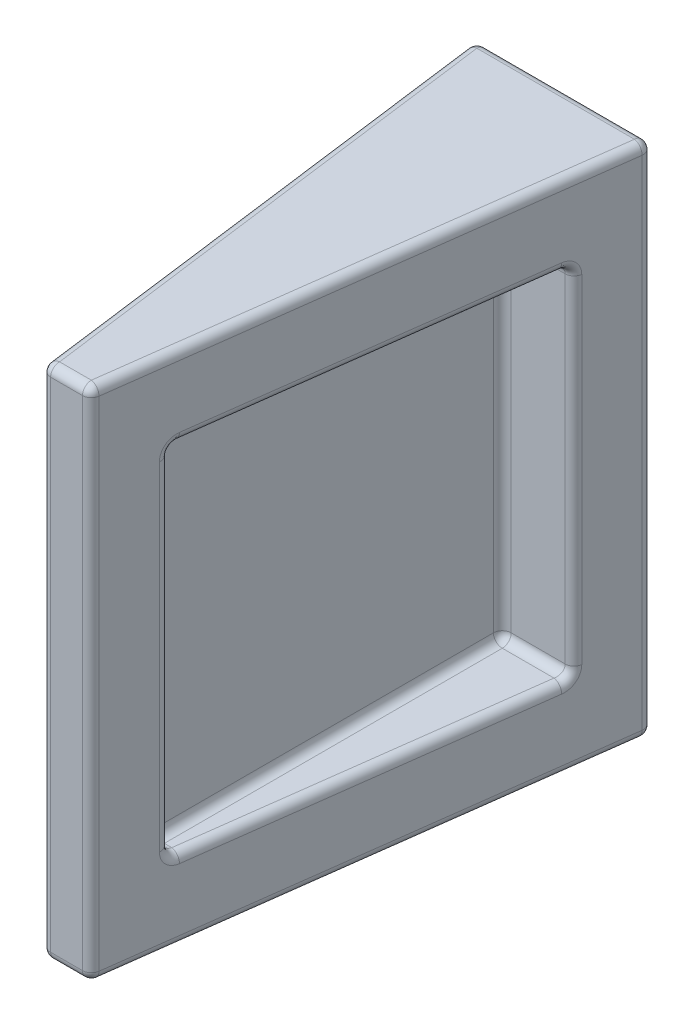
SolidWorks part; units mm, degrees
ref_plane "Front Plane" through (0, 0, 0) normal (1, 0, 0) x (0, 1, 0)
ref_plane "Top Plane" through (0, 0, 0) normal (0, 0, 1) x (0, 1, 0)
ref_plane "Right Plane" through (0, 0, 0) normal (0, 1, 0) x (-1, 0, 0)
sketch "A-Frame Profile" plane through (0, 0, 0) normal (0, 1, 0) x (-1, 0, 0)
  line L0 (-31.75, 0) -> (31.75, 0)
  line L1 (31.75, 0) -> (8.4667, 177.8)
  line L2 (8.4667, 177.8) -> (-8.4667, 177.8)
  line L3 (-8.4667, 177.8) -> (-31.75, 0)
extrude "A-Frame Body" add sketch "A-Frame Profile" along normal blind 92.075 and the other way blind 92.075
sketch "Front Window Sketch" plane through (0, 0, 0) normal (1, 0, 0) x (0, 1, 0)
  line L0 (-63.5, 25.4) -> (63.5, 25.4)
  line L1 (63.5, 25.4) -> (63.5, 152.4)
  line L2 (63.5, 152.4) -> (-63.5, 152.4)
  line L3 (-63.5, 152.4) -> (-63.5, 25.4)
extrude "Front Window Pocket" cut sketch "Front Window Sketch" against normal blind 88.9 from offset 92.075
sketch "Back Window Sketch" plane through (0, 0, 0) normal (1, 0, 0) x (0, 1, 0)
  line L0 (-63.5, 25.4) -> (63.5, 25.4)
  line L1 (63.5, 25.4) -> (63.5, 152.4)
  line L2 (63.5, 152.4) -> (-63.5, 152.4)
  line L3 (-63.5, 152.4) -> (-63.5, 25.4)
extrude "Back Window Pocket" cut sketch "Back Window Sketch" along normal blind 88.9 from offset 92.075 offset against normal yes
sketch "Mounting Holes Sketch" plane through (0, 0, 0) normal (0, 0, 1) x (0, 1, 0)
  circle A0 centre (-31.75, 0) radius 3.9688
  circle A1 centre (31.75, 0) radius 3.9688
extrude "Mounting Holes" cut sketch "Mounting Holes Sketch" along normal blind 12.7
fillet "External Fillets" radius 3.175 40 edges at (3.9688, 31.75, 12.7) (3.9688, 31.75, 0) (3.9688, -31.75, 0) (3.9688, -31.75, 12.7) (-3.175, -63.5, 88.9) (-3.175, 0, 25.4) (-3.175, 63.5, 88.9) (-3.175, 0, 152.4) (-7.4839, -63.5, 152.4) (-7.4839, 63.5, 152.4) (-15.7994, 63.5, 25.4) (-15.7994, -63.5, 25.4) (3.175, -63.5, 88.9) (3.175, 0, 25.4) (3.175, 63.5, 88.9) (3.175, 0, 152.4) (15.7994, -63.5, 25.4) (15.7994, 63.5, 25.4) (7.4839, 63.5, 152.4) (7.4839, -63.5, 152.4) (20.1083, 92.075, 88.9) (0, 92.075, 0) (-20.1083, 92.075, 88.9) (0, 92.075, 177.8) (20.1083, -92.075, 88.9) (0, -92.075, 0) (-20.1083, -92.075, 88.9) (0, -92.075, 177.8) (31.75, 0, 0) (-31.75, 0, 0) (-8.4667, 0, 177.8) (8.4667, 0, 177.8) (28.4238, 0, 25.4) (20.1083, 63.5, 88.9) (11.7929, 0, 152.4) (20.1083, -63.5, 88.9) (-11.7929, 0, 152.4) (-20.1083, 63.5, 88.9) (-28.4238, 0, 25.4) (-20.1083, -63.5, 88.9) tangent propagation no
